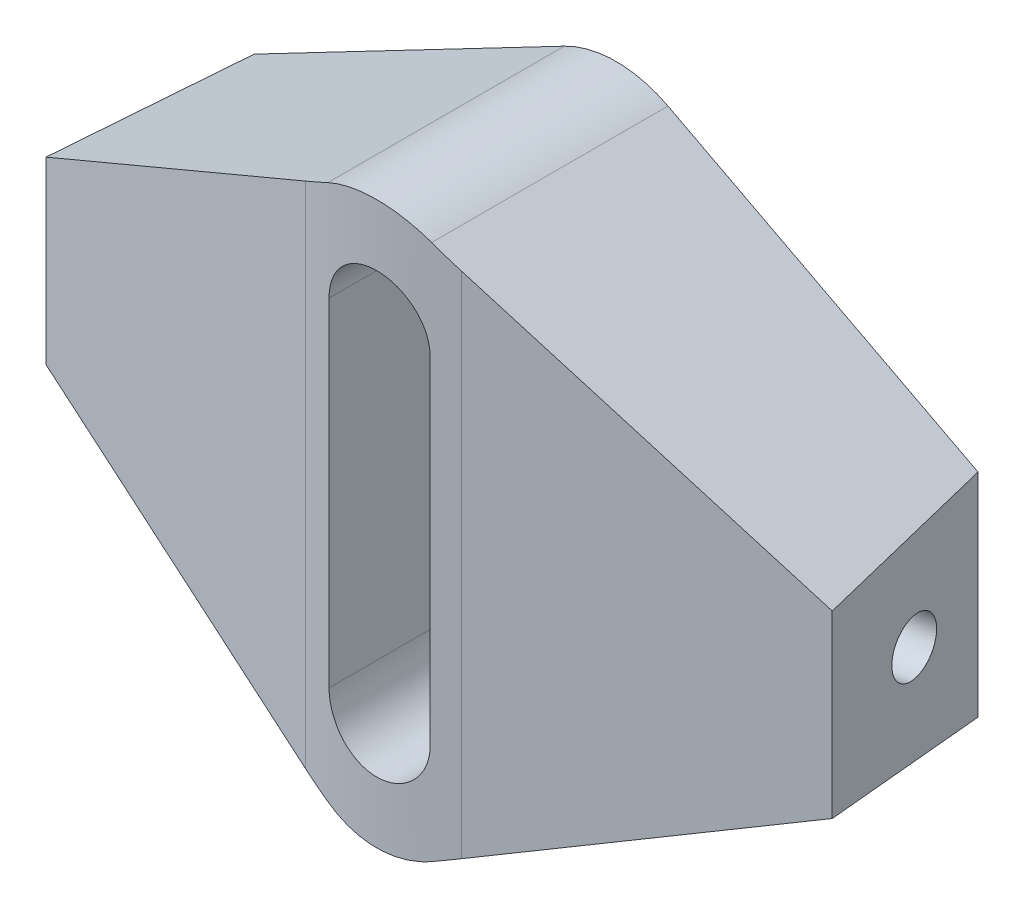
SolidWorks part; units mm, degrees
material "PVC hart"
ref_plane "Ebene vorne" through (0, 0, 0) normal (0, 0, 1) x (1, 0, 0)
ref_plane "Ebene oben" through (0, 0, 0) normal (0, 1, 0) x (1, 0, 0)
ref_plane "Ebene rechts" through (0, 0, 0) normal (1, 0, 0) x (0, 0, -1)
sketch "Skizze3" plane through (0, 0, 0) normal (0, 0, 1) x (1, 0, 0)
  line L0 (-17.5, 4) -> (-2.3088, 11.9334)
  line L1 (0, -7.5124) -> (0, 7.5124) construction
  line L2 (-2.25, -7.5124) -> (-2.25, 7.5124)
  line L3 (2.25, -7.5124) -> (2.25, 7.5124)
  line L4 (-17.5, 0) -> (17.5, 0) construction
  line L5 (-17.5, -4) -> (-2.3088, -11.9334)
  line L6 (0, 12.5) -> (0, -12.5) construction
  line L7 (17.5, -4) -> (2.3088, -11.9334)
  line L8 (-17.5, -4) -> (-17.5, 4)
  line L9 (17.5, 4) -> (2.3088, 11.9334)
  line L10 (17.5, -4) -> (17.5, 4)
  arc A0 (-2.25, -7.5124) -> (2.25, -7.5124) centre (0, -7.5124) ccw
  arc A1 (2.25, 7.5124) -> (-2.25, 7.5124) centre (0, 7.5124) ccw
  arc A2 (-2.3088, 11.9334) -> (2.3088, 11.9334) centre (0, 7.5124) cw
  arc A3 (-2.3088, -11.9334) -> (2.3088, -11.9334) centre (0, -7.5124) ccw
  point P4 (0, 0)
  point P15 (0, 0)
  dimension "D1" = 4.5
  dimension "D2" = 25
  dimension "D4" = 8
  dimension "D5" = 35
extrude "Aufsatz-Linear austragen3" add sketch "Skizze3" along normal blind 20 contours L2 A1 L3 | L8 | L2 | L3 | L10 | L3 A0 L2 region at (-9.7053, 7.5855, 0)
sketch "Skizze10" plane through (0, 0, 0) normal (0, 1, 0) x (1, 0, 0)
  line L0 (-16.1108, 0) -> (-17.5, -7.8785)
  line L1 (-17.5, 0) -> (-2.3088, 0) construction
  line L2 (-17.5, -20) -> (-17.5, 0) construction
  line L3 (-17.5, -7.8785) -> (-3.473, -10.3518)
  line L5 (0, 0) -> (0, -20) construction
  line L6 (2.3088, 0) -> (-2.3088, 0) construction
  line L7 (-2.3088, -20) -> (2.3088, -20) construction
  line L8 (-16.1108, 0) -> (16.1108, 0)
  line L9 (16.1108, 0) -> (17.5, -7.8785)
  line L10 (17.5, -7.8785) -> (3.473, -10.3518)
  arc A0 (-3.473, -10.3518) -> (3.473, -10.3518) centre (0, 9.3443) ccw
  dimension "D3" = 20
  dimension "D1" = 8
  dimension "D2" = 160
extrude "Schnitt-Linear austragen9" cut sketch "Skizze10" against normal through all and the other way through all flip side to cut
sketch "Skizze7" plane through (-16.9833, 0, 4.9479) normal (-0.9848, 0, -0.1736) x (-0.1736, 0, 0.9848)
  line L1 (-5.0242, 0) -> (2.9758, 0) construction
  line L2 (-5.0242, 4.7255) -> (-5.0242, -4.7255) construction
  line L3 (2.9758, -4) -> (2.9758, 4) construction
  circle A0 centre (-1.5242, 0) radius 1.23
  dimension "D1" = 2.46
  dimension "D2" = 4.5
  dimension "D3" = 3.5
extrude "Schnitt-Linear austragen8" cut sketch "Skizze7" against normal blind 12
mirror "Spiegeln4" about plane through (0, 0, 0) normal (1, 0, 0) of "Schnitt-Linear austragen8"
ref_axis "Bewegungsachse" through (0, -11.6078, 0) along (0, 1, 0)
